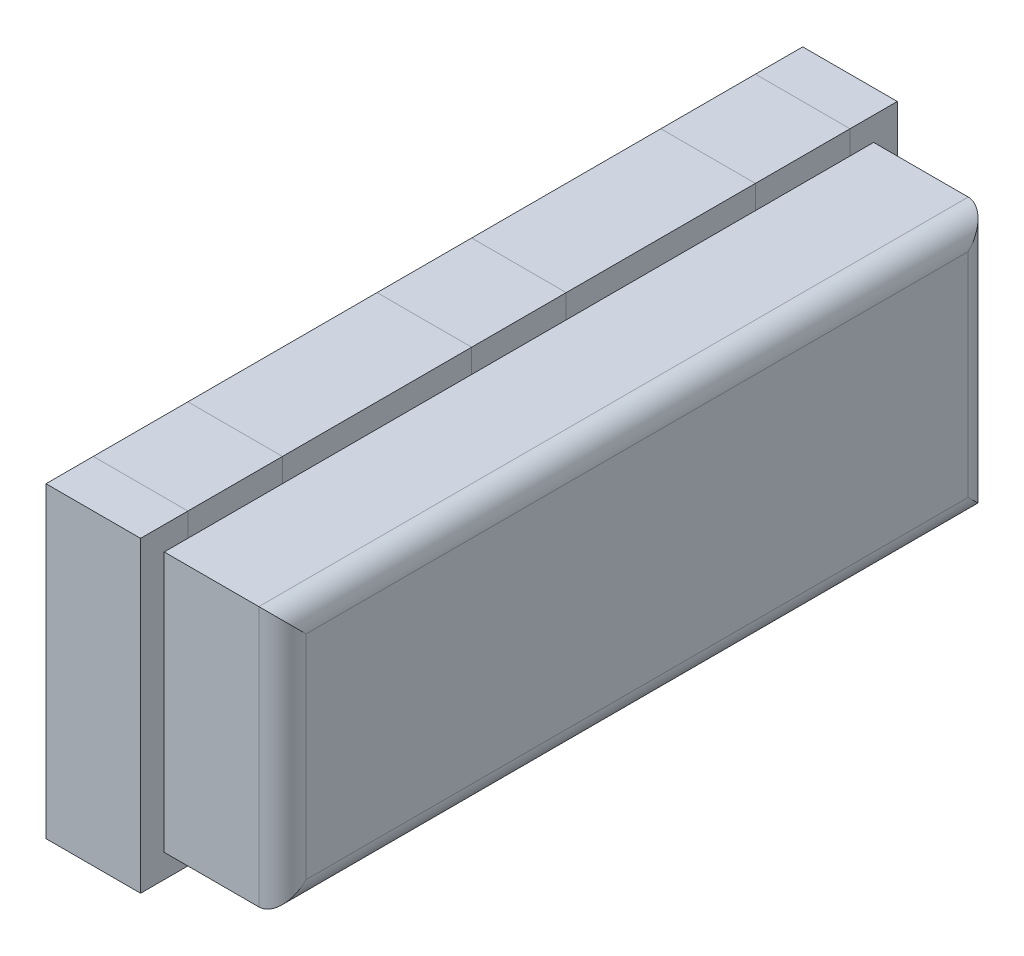
SolidWorks part; units mm, degrees
ref_plane "Front Plane" through (0, 0, 0) normal (0, 0, 1) x (1, 0, 0)
ref_plane "Top Plane" through (0, 0, 0) normal (0, 1, 0) x (1, 0, 0)
ref_plane "Right Plane" through (0, 0, 0) normal (1, 0, 0) x (0, 0, -1)
sketch "Sketch1" plane through (0, 0, 0) normal (1, 0, 0) x (0, 0, -1)
  line L1 (-1.6, 0.65) -> (1.6, 0.65)
  line L2 (-1.6, 0.65) -> (-1.6, -0.65)
  line L3 (-1.6, -0.65) -> (1.6, -0.65)
  line L4 (1.6, 0.65) -> (1.6, -0.65)
  line L5 (-1.6, 0.65) -> (1.6, -0.65) construction
  line L6 (-1.6, -0.65) -> (1.6, 0.65) construction
  point P0 (0, 0)
  dimension "D1" = 3.2
  dimension "D2" = 1.3
extrude "Boss-Extrude1" add sketch "Sketch1" along normal blind 0.4
sketch "Sketch2" plane through (0.4, 0, 0) normal (1, 0, 0) x (0, 0, -1)
  line L1 (-1.5, 0.55) -> (1.5, 0.55)
  line L2 (-1.5, 0.55) -> (-1.5, -0.55)
  line L3 (-1.5, -0.55) -> (1.5, -0.55)
  line L4 (1.5, 0.55) -> (1.5, -0.55)
  line L5 (-1.5, 0.55) -> (1.5, -0.55) construction
  line L6 (-1.5, -0.55) -> (1.5, 0.55) construction
  line L10 (1.6, 0.65) -> (-1.6, 0.65) construction
  point P0 (0, 0)
  dimension "D1" = 3
  dimension "D2" = 0.1
extrude "Boss-Extrude2" add sketch "Sketch2" along normal blind 0.5
sketch "Sketch3" plane through (0, 0, 0) normal (-1, 0, 0) x (0, 0, 1)
  line L0 (1.6, -0.65) -> (-1.6, -0.65) construction
  line L1 (1.4, -0.65) -> (1, -0.65)
  line L2 (1.4, -0.65) -> (1.4, 0.65)
  line L3 (1.4, 0.65) -> (1, 0.65)
  line L4 (1, -0.65) -> (1, 0.65)
  line L5 (-1.6, 0.65) -> (1.6, 0.65) construction
  line L6 (1.6, 0.65) -> (1.6, -0.65) construction
  line L7 (0, -0.495) -> (0, 0.495) construction
  line L8 (0.2, -0.65) -> (-0.2, -0.65)
  line L9 (0.2, -0.65) -> (0.2, 0.65)
  line L10 (0.2, 0.65) -> (-0.2, 0.65)
  line L11 (-0.2, -0.65) -> (-0.2, 0.65)
  line L12 (-1.4, 0.65) -> (-1, 0.65)
  line L13 (-1.4, -0.65) -> (-1, -0.65)
  line L14 (-1, -0.65) -> (-1, 0.65)
  line L15 (-1.4, -0.65) -> (-1.4, 0.65)
  point P8 (1.2, 0.65)
  point P15 (0, -0.65)
  dimension "D1" = 0.4
  dimension "D2" = 0.4
  dimension "D3" = 0.4
  dimension "D4" = 1.2
extrude "Cut-Extrude1" cut sketch "Sketch3" against normal blind 0.4
extrude "Boss-Extrude3" add sketch "Sketch3<2>" against normal blind 0.4 separate body
sketch "Sketch3<2>" plane through (0, 0, 0) normal (-1, 0, 0) x (0, 0, 1) same geometry as "Sketch3"
fillet "Fillet1" radius 0.1 4 edges at (0.9, 0.55, 0) (0.9, 0, 1.5) (0.9, -0.55, 0) (0.9, 0, -1.5)
